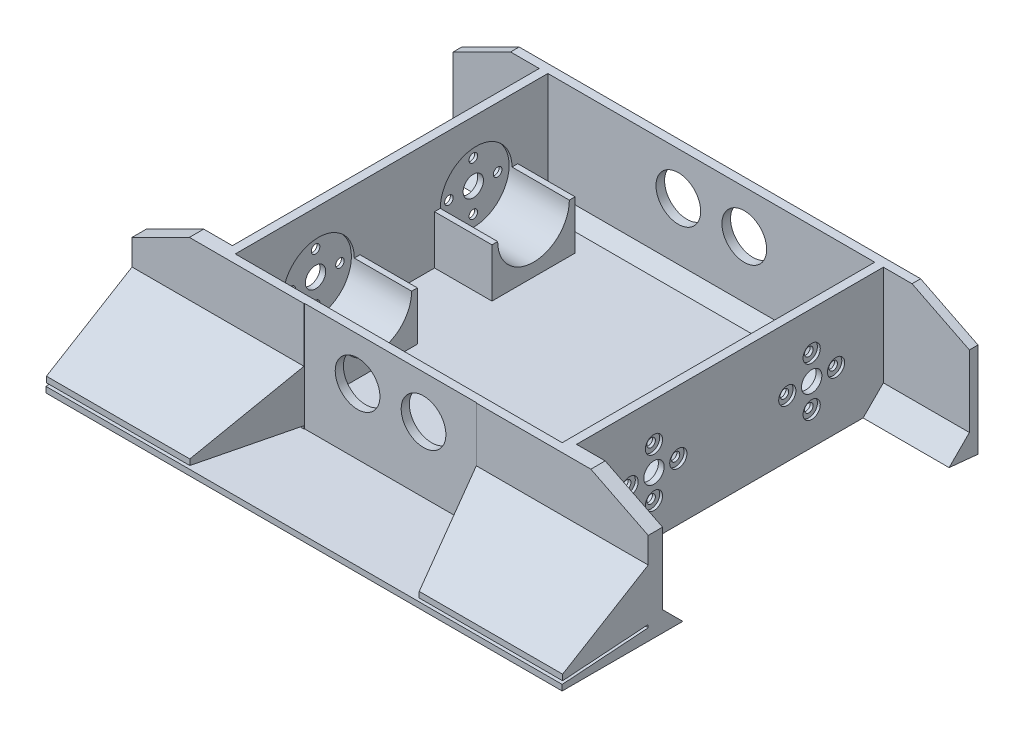
SolidWorks part; units mm, degrees
ref_plane "Front Plane" through (0, 0, 0) normal (0, 0, 1) x (1, 0, 0)
ref_plane "Top Plane" through (0, 0, 0) normal (0, 1, 0) x (1, 0, 0)
ref_plane "Right Plane" through (0, 0, 0) normal (1, 0, 0) x (0, 0, -1)
sketch "Sketch1" plane through (0, 0, 0) normal (0, 1, 0) x (1, 0, 0)
  line L1 (-90, -72.5) -> (90, -72.5)
  line L2 (-90, -72.5) -> (-90, 72.5)
  line L3 (-90, 72.5) -> (90, 72.5)
  line L4 (90, -72.5) -> (90, 72.5)
  line L5 (-90, -72.5) -> (90, 72.5) construction
  line L6 (-90, 72.5) -> (90, -72.5) construction
  point P0 (0, 0)
  dimension "D1" = 180
  dimension "D2" = 145
extrude "Boss-Extrude1" add sketch "Sketch1" along normal blind 2
sketch "Sketch3" plane through (-90, 0, 0) normal (-1, 0, 0) x (0, 0, 1)
  line L0 (72.5, 0) -> (42.5, 0)
  line L1 (-72.5, 0) -> (72.5, 0) construction
  line L2 (42.5, 0) -> (42.5, 4.0978)
  line L3 (42.5, 4.0978) -> (72.5, 2)
  line L4 (72.5, 2) -> (72.5, 0)
  line L5 (-72.5, 2) -> (72.5, 2) construction
  dimension "D1" = 30
  dimension "D2" = 4
extrude "Boss-Extrude2" add sketch "Sketch3" against normal up to surface (180 mm away) up to face at (90, 1, 0)
sketch "Sketch6" plane through (0, 2, 0) normal (0, 1, 0) x (1, 0, 0)
  line L0 (-90, 72.5) -> (90, 72.5)
  line L1 (90, 72.5) -> (90, -42.5)
  line L2 (90, -42.5) -> (-90, -42.5)
  line L3 (-90, -42.5) -> (-90, 72.5)
extrude "Boss-Extrude3" add sketch "Sketch6" along normal blind 40
sketch "Sketch8" plane through (0, 42, 0) normal (0, 1, 0) x (1, 0, 0)
  line L0 (-90, 72.5) -> (-60, 72.5)
  line L1 (90, 72.5) -> (-90, 72.5) construction
  line L6 (0, 0) -> (0, 72.5) construction
  line L9 (90, 72.5) -> (60, 72.5)
  line L17 (-60, 72.5) -> (-60, -37.5)
  line L18 (-60, -37.5) -> (-90, -37.5)
  line L19 (-90, 72.5) -> (-90, -42.5) construction
  line L20 (-90, -37.5) -> (-90, 72.5)
  line L21 (60, 72.5) -> (60, -37.5)
  line L22 (60, -37.5) -> (90, -37.5)
  line L23 (90, -42.5) -> (90, 72.5) construction
  line L24 (90, -37.5) -> (90, 72.5)
  dimension "D1" = 30
  dimension "D2" = 110
  dimension "D3" = 110
extrude "Cut-Extrude3" cut sketch "Sketch8" against normal up to surface (42 mm away) up to face at (0, 0, 0)
shell "Shell1" thickness 3 removed face at (0, 42, 11.25)
sketch "Sketch11" plane through (-57, 0, 0) normal (1, 0, 0) x (0, 0, -1)
  line L0 (72.5, 0) -> (72.5, 42) construction
  line L1 (-37.5, 0) -> (72.5, 0) construction
  line L2 (57, 20) -> (59, 20)
  line L3 (59, 20) -> (59, 0)
  line L4 (59, 0) -> (30, 0)
  line L5 (30, 0) -> (30, 20)
  line L6 (30, 20) -> (32, 20)
  line L7 (2, 20) -> (4, 20)
  line L8 (4, 20) -> (4, 0)
  line L9 (4, 0) -> (-25, 0)
  line L10 (-25, 0) -> (-25, 20)
  line L11 (-25, 20) -> (-23, 20)
  arc A0 (32, 20) -> (57, 20) centre (44.5, 20) ccw
  arc A1 (-23, 20) -> (2, 20) centre (-10.5, 20) ccw
  dimension "D1" = 28
  dimension "D2" = 25
  dimension "D3" = 25
  dimension "D4" = 20
  dimension "D5" = 20
  dimension "D6" = 55
  dimension "D7" = 2
  dimension "D8" = 2
  dimension "D9" = 2
  dimension "D10" = 2
extrude "Boss-Extrude5" add sketch "Sketch11" along normal blind 20
mirror "Mirror1" about plane through (0, 0, 0) normal (1, 0, 0) of "Boss-Extrude5"
sketch "Sketch20" plane through (-57, 0, 0) normal (1, 0, 0) x (0, 0, -1)
  circle A3 centre (-10.5, 20) radius 3.55
  circle A4 centre (44.5, 20) radius 3.55
  circle A5 centre (-2, 20) radius 1.5
  circle A6 centre (-19, 20) radius 1.5
  circle A7 centre (-10.5, 28.5) radius 1.5
  circle A8 centre (-10.5, 11.5) radius 1.5
  circle A9 centre (36, 20) radius 1.5
  circle A10 centre (53, 20) radius 1.5
  circle A11 centre (44.5, 11.5) radius 1.5
  circle A12 centre (44.5, 28.5) radius 1.5
  dimension "D1" = 7.1
  dimension "D2" = 7.1
  dimension "D3" = 3
  dimension "D6" = 17
  dimension "D4" = 17
  dimension "D5" = 17
  dimension "D7" = 17
  dimension "D8" = 8.5
  dimension "D9" = 8.5
  dimension "D10" = 8.5
  dimension "D11" = 8.5
extrude "Cut-Extrude11" cut sketch "Sketch20" along normal up to surface and the other way up to surface up to face at (60, 21, -17.5) other way up to face at (-60, 21, -17.5)
sketch "Sketch21" plane through (60, 0, 0) normal (1, 0, 0) x (0, 0, -1)
  circle A0 centre (-10.5, 28.5) radius 3
  circle A1 centre (-2, 20) radius 3
  circle A2 centre (-19, 20) radius 3
  circle A3 centre (-10.5, 11.5) radius 3
  circle A4 centre (44.5, 28.5) radius 3
  circle A5 centre (53, 20) radius 3
  circle A6 centre (44.5, 11.5) radius 3
  circle A7 centre (36, 20) radius 3
  dimension "D1" = 6
extrude "Cut-Extrude12" cut sketch "Sketch21" against normal blind 1
sketch "Sketch22" plane through (-60, 0, 0) normal (-1, 0, 0) x (0, 0, 1)
  circle A0 centre (-44.5, 28.5) radius 3
  circle A1 centre (-36, 20) radius 3
  circle A2 centre (-44.5, 11.5) radius 3
  circle A3 centre (-53, 20) radius 3
  circle A4 centre (2, 20) radius 3
  circle A5 centre (10.5, 28.5) radius 3
  circle A6 centre (10.5, 11.5) radius 3
  circle A7 centre (19, 20) radius 3
  dimension "D1" = 6
extrude "Cut-Extrude13" cut sketch "Sketch22" against normal blind 1
sketch "Sketch23" plane through (0, 0, 0) normal (1, 0, 0) x (0, 0, -1)
  circle A1 centre (44.5, 20) radius 12.5
  circle A2 centre (-10.5, 20) radius 12.5
  dimension "D1" = 25
  dimension "D2" = 25
extrude "Cut-Extrude14" cut sketch "Sketch23" against normal blind 58 and the other way blind 58
sketch "Sketch24" plane through (-90, 0, 0) normal (-1, 0, 0) x (0, 0, 1)
  line L1 (42.5, 42) -> (42.5, 4.0978) construction
  line L3 (72.3497, 3.013) -> (42.5, 5.1002)
  line L4 (42.5, 5.1002) -> (42.5, 23.0489)
  line L5 (72.5, 2) -> (42.5, 4.0978) construction
  line L6 (42.5, 23.0489) -> (72.3497, 5.013)
  line L7 (72.3497, 5.013) -> (72.3497, 3.013)
  line L8 (72.5, 2) -> (72.5, 0) construction
  dimension "D1" = 34.8755
  dimension "D2" = 1
  dimension "D3" = 2
extrude "Boss-Extrude7" add sketch "Sketch24" against normal up to surface (180 mm away) up to face at (90, 15.0163, 50.8333)
sketch "Sketch25" plane through (0, 42, 0) normal (0, 1, 0) x (1, 0, 0)
  line L0 (-30, -42.3497) -> (30, -42.3497)
  line L4 (90, -72.3497) -> (-90, -72.3497) construction
  line L5 (40, -72.3497) -> (-40, -72.3497)
  line L7 (-40, -72.3497) -> (-30, -42.3497)
  line L8 (40, -72.3497) -> (30, -42.3497)
  dimension "D1" = 80
  dimension "D2" = 30
  dimension "D3" = 60
  dimension "D4" = 30
extrude "Cut-Extrude18" cut sketch "Sketch25" against normal up to surface (39.9895 mm away) up to face at (0, 3.0489, 57.5)
sketch "Sketch26" plane through (-60, 0, 0) normal (-1, 0, 0) x (0, 0, 1)
  line L3 (37.5, 0) -> (-72.5, 0) construction
  line L5 (-72.5, 0) -> (-72.5, 42)
  line L6 (-72.5, 42) -> (-69.5, 42)
  line L7 (-69.5, 42) -> (-69.5, 7.0711)
  line L8 (-69.5, 7.0711) -> (-62.4289, 0)
  line L9 (-72.5, 0) -> (-72.5, -1)
  line L10 (-72.5, -1) -> (-62.4289, 0)
  dimension "D1" = 45
  dimension "D2" = 10
  dimension "D3" = 1
extrude "Boss-Extrude8" add sketch "Sketch26" along normal up to surface and the other way up to surface up to face at (-90, 12.6273, 53.4699) other way up to face at (90, 12.6273, 53.4699)
sketch "Sketch27" plane through (0, 0, 42.5) normal (0, 0, 1) x (1, 0, 0)
  line L0 (-90, 42) -> (-90, 32)
  line L1 (-90, 42) -> (-90, 23.0489) construction
  line L2 (-90, 32) -> (-70, 42)
  line L3 (-90, 42) -> (-30.0501, 42) construction
  line L4 (-70, 42) -> (-90, 42)
  line L5 (90, 42) -> (90, 32)
  line L6 (90, 42) -> (90, 23.0489) construction
  line L7 (90, 32) -> (70, 42)
  line L8 (70, 42) -> (90, 42)
  dimension "D1" = 10
  dimension "D2" = 20
  dimension "D3" = 10
  dimension "D4" = 20
extrude "Cut-Extrude19" cut sketch "Sketch27" against normal up to surface (115 mm away) up to face at (0, 20.5, -72.5)
sketch "Sketch16" plane through (0, 0, 0) normal (0, 0, 1) x (1, 0, 0)
  line L0 (-90, 42) -> (90, 42) construction
  circle A0 centre (-11.5, 27) radius 7.8
  circle A1 centre (11.5, 27) radius 7.8
  point P6 (0, 0)
  dimension "D1" = 15.6
  dimension "D2" = 15.6
  dimension "D5" = 15
  dimension "D3" = 23
  dimension "D4" = 11.5
extrude "Cut-Extrude10" cut sketch "Sketch16" against normal up to surface and the other way up to surface up to face at (0, 24.3333, -72.5) other way up to face at (62.02, 32.4196, 42.5)
sketch "Sketch28" plane through (90, 0, 0) normal (1, 0, 0) x (0, 0, -1)
  line L0 (-37.5, 0) -> (-37.5, 7.0711)
  line L1 (-37.5, 0) -> (-37.5, 42) construction
  line L2 (-37.5, 7.0711) -> (-30.4289, 0)
  line L3 (62.4289, 0) -> (-37.5, 0) construction
  line L4 (-30.4289, 0) -> (-37.5, 0)
  dimension "D1" = 10
  dimension "D2" = 45
extrude "Boss-Extrude9" add sketch "Sketch28" against normal up to surface (180 mm away) up to face at (-90, 10.6273, 53.4699)
sketch "Sketch4" plane through (0, 7.0353, 0.492) normal (0, 0.9976, 0.0698) x (1, 0, 0)
  line L0 (-90, -72.1839) -> (-90, -42.1106) construction
  line L1 (90, -42.1106) -> (90, -72.1839) construction
  line L4 (-90, -72.1839) -> (90, -72.1839) construction
  circle A0 centre (-76.5, -49.1839) radius 1.5
  circle A1 centre (-76.5, -66.1839) radius 1.5
  circle A2 centre (76.5, -49.1839) radius 1.5
  circle A3 centre (76.5, -66.1839) radius 1.5
  dimension "D1" = 3
  dimension "D3" = 13.5
  dimension "D5" = 13.5
  dimension "D7" = 6
  dimension "D6" = 17
extrude "Cut-Extrude1" cut sketch "Sketch4" against normal up to surface and the other way blind 5 up to face at (0, 0, 17.7322)
